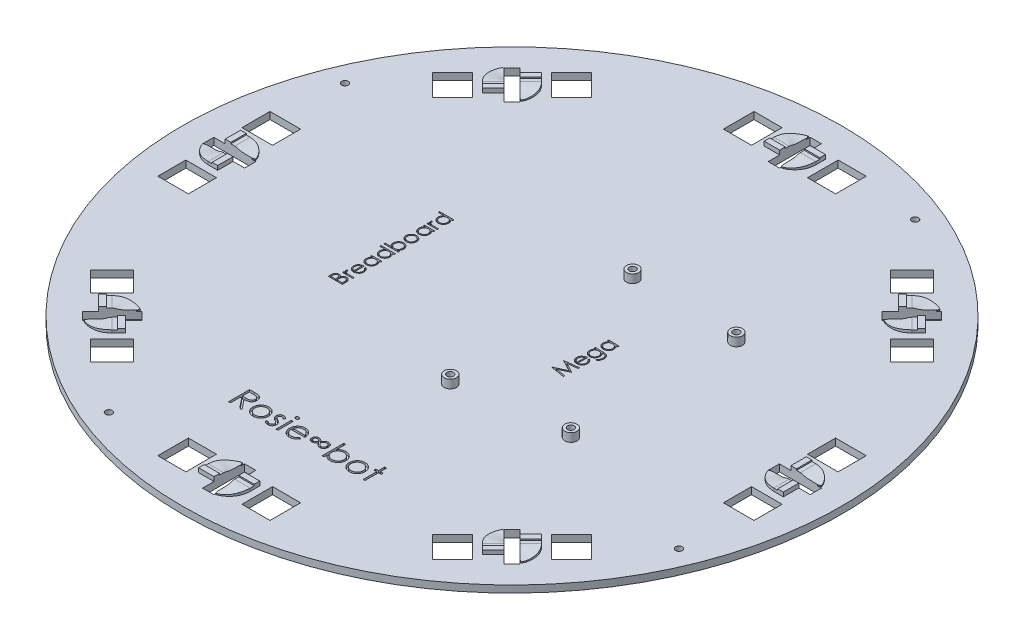
SolidWorks part; units mm, degrees
ref_plane "Front" through (0, 0, 0) normal (0, 0, 1) x (1, 0, 0)
ref_plane "Top" through (0, 0, 0) normal (0, 1, 0) x (1, 0, 0)
ref_plane "Right" through (0, 0, 0) normal (1, 0, 0) x (0, 0, -1)
sketch "Sketch1" plane through (0, 0, 0) normal (0, 1, 0) x (1, 0, 0)
  circle A0 centre (0, 0) radius 149.225
  dimension "D1" = 298.45
extrude "Base" add sketch "Sketch1" along normal blind 3.175 contours A0
sketch "Sketch2" plane through (0, 3.175, 0) normal (0, 1, 0) x (1, 0, 0)
  line L1 (-2.54, -137.5833) -> (2.54, -137.5833)
  line L2 (-2.54, -137.5833) -> (-2.54, -118.5333)
  line L3 (-2.54, -118.5333) -> (2.54, -118.5333)
  line L4 (2.54, -137.5833) -> (2.54, -118.5333)
  circle A0 centre (0, 0) radius 149.225 construction
  point P4 (0, -118.5333)
  dimension "D1" = 5.08
  dimension "D2" = 19.05
  dimension "D3" = 137.5833
extrude "Cut-Extrude1" cut sketch "Sketch2" against normal up to next and the other way through all contours L1 L4 L3 L2
sketch "Sketch4" plane through (0, 3.175, 0) normal (0, 1, 0) x (1, 0, 0)
  line L0 (0, -128.0583) -> (-2.9434, -118.9995) construction
  line L1 (-2.9434, -118.9995) -> (0, -128.0583) construction
  line L2 (0, -128.0583) -> (-5.5987, -120.3525) construction
  line L3 (0, -128.0583) -> (-7.7059, -122.4597) construction
  line L4 (0, -128.0583) -> (-9.0588, -125.115) construction
  line L5 (0, -128.0583) -> (-9.525, -128.0583) construction
  line L9 (2.54, -118.5333) -> (-2.54, -118.5333) construction
  line L10 (2.54, -118.5333) -> (2.54, -137.5833) construction
  line L11 (-2.54, -118.5333) -> (-2.54, -137.5833) construction
  line L12 (2.54, -137.5833) -> (-2.54, -137.5833) construction
  circle A0 centre (0, -128.0583) radius 9.525 construction
  point P16 (0, -118.5333)
  point P19 (2.54, -128.0583)
  dimension "D1" = 18
  dimension "D2" = 18
  dimension "D3" = 18
  dimension "D4" = 18
  dimension "D5" = 18
ref_plane "Plane1" through (-37.6354, 0, 12.2285) normal (0.9511, 0, -0.309) x (-0.309, 0, -0.9511)
ref_plane "Plane2" through (-60.8954, 0, 44.2431) normal (0.809, 0, -0.5878) x (-0.5878, 0, -0.809)
ref_plane "Plane3" through (-60.8954, 0, 83.8153) normal (0.5878, 0, -0.809) x (-0.809, 0, -0.5878)
ref_plane "Plane4" through (-37.6354, 0, 115.8299) normal (0.309, 0, -0.9511) x (-0.9511, 0, -0.309)
ref_plane "Plane5" through (0, 0, 128.0583) normal (0, 0, -1) x (-1, 0, 0)
sketch "Sketch5" plane through (-37.6354, 0, 12.2285) normal (0.9511, 0, -0.309) x (-0.309, 0, -0.9511)
  line L0 (-111.947, 3.175) -> (-130.0646, 3.175) construction
  line L1 (-113.5711, 3.175) -> (-112.2657, 3.175)
  line L2 (-113.5711, 3.175) -> (-113.5711, 3.683)
  line L3 (-113.5711, 3.683) -> (-112.2657, 3.683)
  line L4 (-112.2657, 3.175) -> (-112.2657, 3.683)
  dimension "D2" = 0.508
sketch "Sketch6" plane through (-60.8954, 0, 44.2431) normal (0.809, 0, -0.5878) x (-0.5878, 0, -0.809)
  line L0 (-94.4025, 3.175) -> (-109.8143, 3.175) construction
  line L1 (-99.2801, 3.175) -> (-94.0764, 3.175)
  line L2 (-99.2801, 3.175) -> (-99.2801, 3.775)
  line L3 (-99.2801, 3.775) -> (-94.0764, 3.775)
  line L4 (-94.0764, 3.175) -> (-94.0764, 3.775)
  dimension "D2" = 0.6
sketch "Sketch7" plane through (-60.8954, 0, 83.8153) normal (0.5878, 0, -0.809) x (-0.809, 0, -0.5878)
  line L0 (-67.6172, 3.175) -> (-78.8146, 3.175) construction
  line L1 (-72.1312, 3.175) -> (-65.7458, 3.175)
  line L2 (-72.1312, 3.175) -> (-72.1312, 4.075)
  line L3 (-72.1312, 4.075) -> (-65.7458, 4.075)
  line L4 (-65.7458, 3.175) -> (-65.7458, 4.075)
  dimension "D2" = 0.9
sketch "Sketch10" plane through (-37.6354, 0, 115.8299) normal (0.309, 0, -0.9511) x (-0.9511, 0, -0.309)
  line L0 (-39.5722, 3.175) -> (-30.5134, 3.175) construction
  line L1 (-36.9015, 3.175) -> (-30.0472, 3.175)
  line L2 (-36.9015, 3.175) -> (-36.9015, 4.375)
  line L3 (-36.9015, 4.375) -> (-30.0472, 4.375)
  line L4 (-30.0472, 3.175) -> (-30.0472, 4.375)
  dimension "D3" = 1.2
sketch "Sketch11" plane through (0, 0, 128.0583) normal (0, 0, -1) x (-1, 0, 0)
  line L0 (0, 3.175) -> (9.525, 3.175) construction
  line L1 (2.54, 3.175) -> (9.525, 3.175)
  line L2 (2.54, 3.175) -> (2.54, 4.475)
  line L3 (2.54, 4.475) -> (9.525, 4.475)
  line L4 (9.525, 3.175) -> (9.525, 4.475)
  dimension "D3" = 1.3
loft "Loft1" add profiles "Sketch5", "Sketch6", "Sketch7", "Sketch10", "Sketch11" connector at (-2.54, 3.683, 120.241) connector at (-2.54, 3.775, 124.5623) connector at (-2.54, 4.075, 126.2129) connector at (-2.54, 4.375, 127.233) connector at (-2.54, 4.475, 128.0583)
sketch "Sketch13" plane through (-104.9799, 0, 128.0583) normal (0, 0, -1) x (-1, 0, 0)
  line L6 (-95.4549, 3.175) -> (-102.4399, 3.175)
  line L7 (-95.4549, 3.175) -> (-95.4549, 4.475)
  line L8 (-95.4549, 4.475) -> (-102.4399, 4.475)
  line L9 (-102.4399, 3.175) -> (-102.4399, 4.475)
extrude "Boss-Extrude4" add sketch "Sketch13" against normal blind 1.7907
sketch "Sketch25" plane through (0, 0, 129.849) normal (0, 0, 1) x (1, 0, 0)
  line L0 (-9.525, 4.475) -> (-2.54, 4.475) construction
  line L1 (-9.525, 3.175) -> (-2.54, 3.175)
  line L2 (-9.525, 3.175) -> (-9.525, 5.075)
  line L3 (-9.525, 5.075) -> (-2.54, 5.075)
  line L4 (-2.54, 3.175) -> (-2.54, 5.075)
  dimension "D1" = 0.6
extrude "Boss-Extrude5" add sketch "Sketch25" along normal blind 2.54
sketch "Sketch14" plane through (-2.54, 0, 0) normal (1, 0, 0) x (0, 0, -1)
  line L0 (-128.0583, 3.175) -> (-128.0583, 0) construction
  line L1 (-118.5333, 0) -> (-137.5833, 0) construction
ref_plane "Plane6" through (0, 0, 0) normal (1, 0, 0) x (0, 0, -1)
sketch "Sketch15" plane through (0, 0, 0) normal (1, 0, 0) x (0, 0, -1)
  line L0 (-128.0583, 0) -> (-128.0583, 3.175) construction
pattern_circular "CirPattern1" count 2 over 360 about axis through (0, 0, 128.0583) along (0, 1, 0) of "Loft1", "Boss-Extrude5", "Boss-Extrude4" reverse direction yes
ref_axis "Axis1" through (0, 50, 0) along (0, -1, 0)
pattern_circular "CirPattern5" count 8 over 360 about axis through (0, 50, 0) along (0, -1, 0) of "CirPattern1", "Cut-Extrude1"
sketch "Sketch18" plane through (0, 3.175, 0) normal (0, 1, 0) x (1, 0, 0)
  line L0 (12.7, 40.64) -> (60.96, 40.64) construction
  line L1 (12.7, 40.64) -> (12.7, -40.64) construction
  line L2 (60.96, -34.29) -> (12.7, -34.29) construction
  line L3 (60.96, -34.29) -> (60.96, 40.64) construction
  line L4 (0, -149.225) -> (0, 149.225) construction
  line L5 (0, -1.7463) -> (0, 1.7463) construction
  line L6 (-149.225, 0) -> (149.225, 0) construction
  line L7 (12.7, 41.91) -> (12.7, 40.64) construction
  circle A0 centre (12.7, 41.91) radius 2.77
  circle A1 centre (12.7, -40.64) radius 2.77
  circle A2 centre (60.96, -34.29) radius 2.77
  circle A3 centre (60.96, 40.64) radius 2.77
  circle A4 centre (12.7, -40.64) radius 1.5
  circle A5 centre (12.7, 41.91) radius 1.5
  circle A6 centre (60.96, 40.64) radius 1.5
  circle A7 centre (60.96, -34.29) radius 1.5
  circle A8 centre (0, 0) radius 149.225 construction
  point P22 (12.7, 0)
  dimension "D7" = 12.7
  dimension "D5" = 3
  dimension "D6" = 1.27
  dimension "D1" = 82.55
  dimension "D2" = 74.93
  dimension "D3" = 48.26
  dimension "D4" = 1.27
sketch "Sketch19" plane through (0, 3.175, 0) normal (0, 1, 0) x (1, 0, 0)
  line L0 (-53.4609, -129.066) -> (0, 0) construction
  line L1 (0, -149.225) -> (0, 149.225) construction
  circle A1 centre (-53.4609, -129.066) radius 1.5
  dimension "D1" = 139.7
  dimension "D4" = 3
  dimension "D5" = 22.5
extrude "Cut-Extrude2" cut sketch "Sketch19" against normal through all
pattern_circular "CirPattern7" count 4 over 360 about axis through (0, 50, 0) along (0, -1, 0) of "Cut-Extrude2"
extrude "MegaScrews" add sketch "Sketch18" along normal blind 3.81
sketch "Sketch23" plane through (0, 3.175, 0) normal (0, 1, 0) x (1, 0, 0)
  line L9 (-2.54, -132.389) -> (-2.54, -137.5833) construction
  line L10 (-25.4, -121.1305) -> (-12.7, -121.1305)
  line L11 (-25.4, -121.1305) -> (-25.4, -134.9862)
  line L16 (-25.4, -134.9862) -> (-12.7, -134.9862)
  line L17 (-12.7, -121.1305) -> (-12.7, -134.9862)
  line L19 (2.54, -118.5333) -> (2.54, -123.7276) construction
  line L20 (0, -50) -> (0, 50) construction
  line L21 (12.7, -121.1305) -> (12.7, -134.9862)
  line L22 (25.4, -134.9862) -> (12.7, -134.9862)
  line L23 (25.4, -121.1305) -> (25.4, -134.9862)
  line L24 (25.4, -121.1305) -> (12.7, -121.1305)
  point P8 (-2.54, -134.9862)
  point P9 (2.54, -121.1305)
  dimension "D1" = 12.7
  dimension "D2" = 10.16
extrude "Cut-Extrude6" cut sketch "Sketch23" against normal through all
pattern_circular "CirPattern8" count 8 over 360 about axis through (0, 50, 0) along (0, -1, 0) of "Cut-Extrude6"
sketch "Sketch17" plane through (0, 3.175, 0) normal (0, 1, 0) x (1, 0, 0)
  line L0 (-31.75, -97.8162) -> (31.75, -97.8162) construction
  point P3 (0, -97.8162)
  dimension "D2" = 97.8162
  dimension "D1" = 63.5
sketch "Sketch16" plane through (0, 3.175, 0) normal (0, 1, 0) x (1, 0, 0)
  line L0 (-31.75, -97.8162) -> (31.75, -97.8162) construction
  text T0 "Rosie∞bot\r\n" font "Century Gothic" height in points 36
extrude "Cut-Extrude4" cut sketch "Sketch16" against normal blind 1.27
sketch "Sketch22" plane through (0, 3.175, 0) normal (0, 1, 0) x (1, 0, 0)
  line L0 (-50.8, 25.1735) -> (-50.8, -31.2294) construction
  text T0 "Breadboard"
  dimension "D1" = 50.8
extrude "Cut-Extrude5" cut sketch "Sketch22" against normal blind 1.27
sketch "Sketch24" plane through (0, 3.175, 0) normal (0, 1, 0) x (1, 0, 0)
  line L0 (35.4114, -12.631) -> (36.0762, 12.631) construction
  circle A0 centre (12.7, 41.91) radius 1.5 construction
  circle A1 centre (60.96, 40.64) radius 1.5 construction
  text T0 "Mega"
  point P12 (35.7438, 0)
extrude "Cut-Extrude7" cut sketch "Sketch24" against normal blind 1.27
